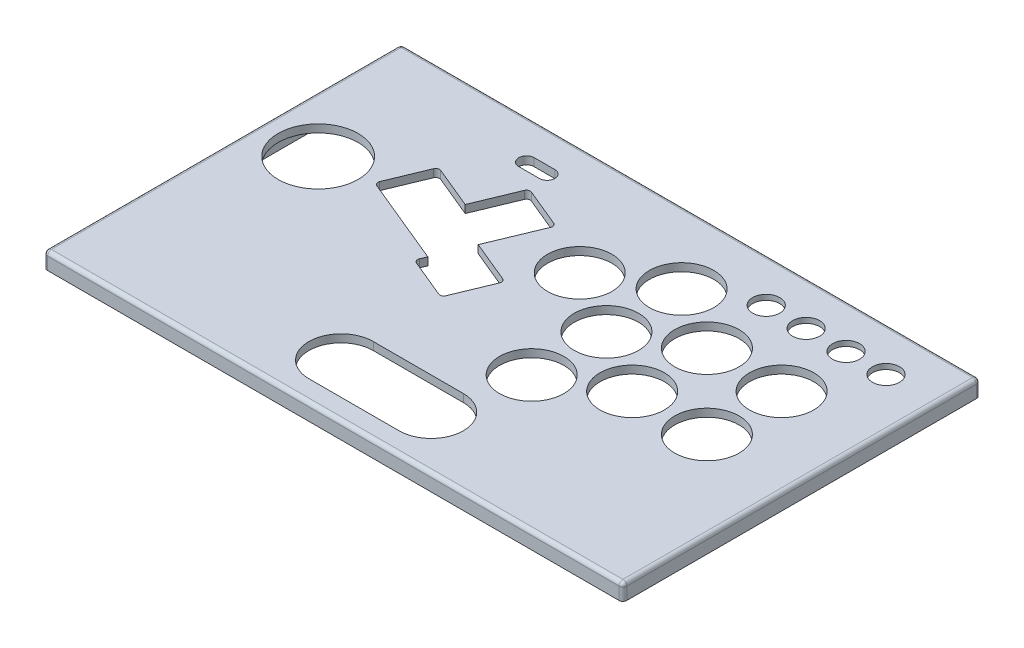
SolidWorks part; units mm, degrees
ref_plane "Front Plane" through (0, 0, 0) normal (0, 0, 1) x (1, 0, 0)
ref_plane "Top Plane" through (0, 0, 0) normal (0, 1, 0) x (1, 0, 0)
ref_plane "Right Plane" through (0, 0, 0) normal (1, 0, 0) x (0, 0, -1)
sketch "Button Cutouts" plane through (0, 0, 0) normal (0, 1, 0) x (1, 0, 0)
  line L0 (24.5, 61) -> (24.5, 32) construction
  line L1 (298.8548, 529.5585) -> (1494.2739, 529.5585) construction
  line L12 (-36.2591, 48.1292) -> (-29.3708, 64.7591) construction
  line L20 (49.5, 75) -> (49.5, 46) construction
  line L21 (78.5, 75) -> (78.5, 46) construction
  line L22 (17.5, 0) -> (-17.5, 0) construction
  line L28 (-36.2591, 48.1292) -> (-19.6292, 41.2409) construction
  line L29 (17.5, -12.5) -> (-17.5, -12.5)
  line L30 (17.5, 12.5) -> (-17.5, 12.5)
  line L31 (24.6803, 89.9994) -> (49.5, 75) construction
  line L32 (24.6803, 89.9994) -> (24.5, 61) construction
  line L33 (-0.5241, 75.6559) -> (24.6803, 89.9994) construction
  line L34 (-0.5241, 75.6559) -> (24.5, 61) construction
  line L48 (-29.3708, 64.7591) -> (-12.7409, 57.8708) construction
  line L49 (-19.6292, 41.2409) -> (-12.7409, 57.8708) construction
  line L50 (-36.2591, 48.1292) -> (-12.7409, 57.8708) construction
  line L51 (-29.3708, 64.7591) -> (-19.6292, 41.2409) construction
  line L52 (-35.6984, 52.2266) -> (-28.8101, 68.8564) construction
  line L53 (-35.6984, 52.2266) -> (-52.3282, 59.1149) construction
  line L54 (-28.8101, 68.8564) -> (-45.4399, 75.7447) construction
  line L55 (-52.3282, 59.1149) -> (-45.4399, 75.7447) construction
  line L56 (-35.6984, 52.2266) -> (-45.4399, 75.7447) construction
  line L57 (-28.8101, 68.8564) -> (-52.3282, 59.1149) construction
  line L58 (-69.9281, 66.405) -> (-63.0398, 83.0348) construction
  line L59 (-69.9281, 66.405) -> (-53.2983, 59.5167) construction
  line L60 (-63.0398, 83.0348) -> (-46.41, 76.1465) construction
  line L61 (-53.2983, 59.5167) -> (-46.41, 76.1465) construction
  line L62 (-69.9281, 66.405) -> (-46.41, 76.1465) construction
  line L63 (-63.0398, 83.0348) -> (-53.2983, 59.5167) construction
  line L64 (-40.5692, 63.9856) -> (-22.9693, 56.6955) construction
  line L65 (-40.5692, 63.9856) -> (-58.1691, 71.2758) construction
  line L66 (-45.0381, 76.7148) -> (-38.1498, 93.3446) construction
  line L67 (-45.0381, 76.7148) -> (-28.4083, 69.8265) construction
  line L68 (-38.1498, 93.3446) -> (-21.52, 86.4563) construction
  line L69 (-28.4083, 69.8265) -> (-21.52, 86.4563) construction
  line L70 (-45.0381, 76.7148) -> (-21.52, 86.4563) construction
  line L71 (-38.1498, 93.3446) -> (-28.4083, 69.8265) construction
  line L72 (-40.5692, 63.9856) -> (-33.2791, 81.5855) construction
  line L73 (-24.5, 53) -> (-22.9693, 56.6955) construction
  line L74 (-58.1691, 71.2758) -> (-65.4592, 53.6759) construction
  line L75 (-65.4592, 53.6759) -> (-90.4039, 64.0083) construction
  line L76 (-70.5814, 66.1344) -> (-63.3104, 83.6881)
  line L77 (-63.3104, 83.6881) -> (-45.7105, 76.398)
  line L78 (-45.7105, 76.398) -> (-38.4204, 93.9979)
  line L79 (-38.4204, 93.9979) -> (-20.8667, 86.7269)
  line L80 (-20.8667, 86.7269) -> (-29.6876, 65.4315)
  line L81 (-29.6876, 65.4315) -> (-12.0877, 58.1414)
  line L82 (-12.0877, 58.1414) -> (-19.3586, 40.5877)
  line L83 (-19.3586, 40.5877) -> (-36.9123, 47.8586)
  line L84 (-36.9123, 47.8586) -> (-35.3816, 51.5542)
  line L85 (-35.3816, 51.5542) -> (-70.5814, 66.1344)
  line L86 (-66.484, 74.7199) -> (-66.9459, 74.9112) construction
  line L87 (-29.6436, 90.3624) -> (-29.8349, 89.9005) construction
  line L88 (-16.1851, 49.5558) -> (-15.7231, 49.3645) construction
  line L89 (-33.2791, 140.3317) -> (-33.2791, 81.5855) construction
  circle A0 centre (24.5, 32) radius 12.5
  circle A1 centre (24.5, 61) radius 12.5
  circle A2 centre (49.5, 46) radius 12.5
  circle A3 centre (49.5, 75) radius 12.5
  circle A4 centre (78.5, 75) radius 12.5
  circle A5 centre (78.5, 46) radius 12.5
  arc A8 (17.5, -12.5) -> (17.5, 12.5) centre (17.5, 0) ccw
  arc A9 (-17.5, 12.5) -> (-17.5, -12.5) centre (-17.5, 0) ccw
  circle A10 centre (-90.4039, 64.0083) radius 15.5
  circle A11 centre (24.6803, 89.9994) radius 12.5
  circle A12 centre (-0.5241, 75.6559) radius 12.5
  point P1 (-24.5, 53)
  point P5 (-40.5692, 63.9856)
  point P6 (-58.1691, 71.2758)
  point P37 (0, 0)
  point P45 (-33.2791, 81.5855)
  point P54 (-30, 0)
  point P55 (30, 0)
  dimension "D2" = 25
  dimension "D12" = 12.5
  dimension "D18" = 31
  dimension "D25" = 22.5
  dimension "D1" = 29
  dimension "D3" = 25
  dimension "D4" = 29
  dimension "D5" = 14
  dimension "D6" = 18
  dimension "D7" = 19.05
  dimension "D8" = 53
  dimension "D9" = 7
  dimension "D10" = 4
  dimension "D11" = 27
  dimension "D13" = 32
  dimension "D14" = 7
  dimension "D15" = 19.05
  dimension "D16" = 0.5
  dimension "D17" = 60
  dimension "D19" = 0.5
  dimension "D20" = 0.5
  dimension "D21" = 29
  dimension "D22" = 29
  dimension "D23" = 0.5
  dimension "D24" = 0.5
sketch "Sketch2" plane through (0, 0, 0) normal (0, 1, 0) x (1, 0, 0)
  line L0 (-105.9039, 64.0083) -> (-112.4039, 64.0083) construction
  line L1 (-112.4039, 118.1994) -> (112.4039, 118.1994)
  line L2 (-112.4039, 118.1994) -> (-112.4039, -20.5)
  line L3 (-112.4039, -20.5) -> (112.4039, -20.5)
  line L4 (112.4039, 118.1994) -> (112.4039, -20.5)
  line L5 (24.6803, 102.4994) -> (24.6803, 118.1994) construction
  line L6 (0, -12.5) -> (0, -20.5) construction
  line L7 (17.5, -12.5) -> (-17.5, -12.5) construction
  circle A0 centre (-90.4039, 64.0083) radius 15.5 construction
  circle A2 centre (24.6803, 89.9994) radius 12.5 construction
  point P4 (0, -20.5)
  dimension "D2" = 6.5
  dimension "D1" = 8
  dimension "D3" = 15.7
  dimension "D4" = 224.8079
  dimension "D5" = 138.6994
extrude "top plate" add sketch "Sketch2" along normal blind 6.35
extrude "primary button cutouts" cut sketch "Button Cutouts" along normal up to next
fillet "Fillet1" radius 1.5 7 edges at (-20.8667, 3.175, -86.7269) (-12.0877, 3.175, -58.1414) (-19.3586, 3.175, -40.5877) (-36.9123, 3.175, -47.8586) (-70.5814, 3.175, -66.1344) (-63.3104, 3.175, -83.6881) (-38.4204, 3.175, -93.9979)
sketch "Sketch4" plane through (0, 0, 0) normal (0, -1, 0) x (1, 0, 0)
  line L0 (112.4039, 20.5) -> (112.4039, -118.1994) construction
  line L1 (-106.4039, 14.5) -> (106.4039, 14.5)
  line L2 (-106.4039, 14.5) -> (-106.4039, -112.1994)
  line L3 (-106.4039, -112.1994) -> (106.4039, -112.1994)
  line L4 (106.4039, 14.5) -> (106.4039, -112.1994)
  line L5 (-112.4039, 20.5) -> (112.4039, 20.5) construction
  line L6 (112.4039, -118.1994) -> (-112.4039, -118.1994) construction
  line L7 (-112.4039, -118.1994) -> (-112.4039, 20.5) construction
  dimension "D1" = 6
  dimension "D2" = 6
  dimension "D3" = 6
  dimension "D4" = 6
extrude "Cut-Extrude2" cut sketch "Sketch4" against normal blind 3.3
fillet "Fillet2" radius 1.5 8 edges at (112.4039, 3.175, -118.1994) (-112.4039, 3.175, -118.1994) (-112.4039, 3.175, 20.5) (112.4039, 3.175, 20.5) (112.4039, 6.35, -48.8497) (0, 6.35, -118.1994) (0, 6.35, 20.5) (-112.4039, 6.35, -48.8497)
hole_wizard "Tap Drill for M3x0.5 Tap1" positions "3DSketch1" profile "Sketch6" hole size "M3x0.5" standard "ANSI Metric"
sketch3d "3DSketch1"
  line L0 (-108.4039, 0, 16.5) -> (-108.4039, 0, 20.5) construction
  line L1 (-110.9039, 0, 20.5) -> (110.9039, 0, 20.5) construction
  line L3 (-108.4039, 0, 16.5) -> (-112.4039, 0, 16.5)
  line L4 (-112.4039, 0, -116.6994) -> (-112.4039, 0, 19) construction
  line L6 (108.4039, 0, -114.1994) -> (112.4039, 0, -114.1994)
  line L7 (112.4039, 0, 19) -> (112.4039, 0, -116.6994) construction
  line L9 (108.4039, 0, -114.1994) -> (108.4039, 0, -118.1994)
  line L10 (110.9039, 0, -118.1994) -> (-110.9039, 0, -118.1994) construction
  point P0 (-108.4039, 0, 16.5)
  point P2 (-108.4039, 0, -114.1994)
  point P4 (108.4039, 0, -114.1994)
  point P6 (108.4039, 0, 16.5)
  dimension "D1" = 4
sketch "Sketch6" plane through (-108.4039, 0, 16.5) normal (1, 0, 0) x (0, 0, -1)
  line L0 (0, 0) -> (0, 4.7511)
  line L1 (0, 4.7511) -> (1.25, 4)
  line L2 (1.25, 4) -> (1.25, 0)
  line L5 (1.25, 0) -> (0, 0)
  line L10 (0, 4.7511) -> (-1.25, 4) construction
  line L11 (0, -6.35) -> (0, 107.95) construction
  dimension "Hole Dia." = 2.5
  dimension "Hole Depth" = 4
  dimension "Drill Angle" = 118
sketch "Sketch7" plane through (0, 6.35, 0) normal (0, 1, 0) x (1, 0, 0)
  circle A0 centre (46.5961, 100.92) radius 5.25
  circle A1 centre (62.0961, 100.92) radius 5.25
  circle A2 centre (77.5961, 100.92) radius 5.25
  circle A3 centre (93.0961, 100.92) radius 5.25
  dimension "D1" = 10.5
extrude "extra_buttons" cut sketch "Sketch7" against normal up to next
sketch "Sketch8" plane through (0, 6.35, 0) normal (0, 1, 0) x (1, 0, 0)
  line L0 (-48.0625, 102.5336) -> (-40.0625, 102.5336) construction
  line L1 (-48.0625, 105.5336) -> (-40.0625, 105.5336)
  line L2 (-48.0625, 99.5336) -> (-40.0625, 99.5336)
  arc A0 (-48.0625, 105.5336) -> (-48.0625, 99.5336) centre (-48.0625, 102.5336) ccw
  arc A1 (-40.0625, 99.5336) -> (-40.0625, 105.5336) centre (-40.0625, 102.5336) ccw
  point P2 (-44.0625, 102.5336)
  dimension "D1" = 8
  dimension "D2" = 6
extrude "led_cutout" cut sketch "Sketch8" against normal up to next
sketch "Sketch9" plane through (0, 3.3, 0) normal (0, -1, 0) x (-1, 0, 0)
  line L0 (-93.0961, 100.92) -> (-46.5961, 100.92) construction
  line L1 (-93.0961, 110.92) -> (-46.5961, 110.92)
  line L2 (-93.0961, 90.92) -> (-46.5961, 90.92)
  arc A0 (-93.0961, 110.92) -> (-93.0961, 90.92) centre (-93.0961, 100.92) ccw
  arc A1 (-46.5961, 90.92) -> (-46.5961, 110.92) centre (-46.5961, 100.92) ccw
  circle A2 centre (-93.0961, 100.92) radius 5.25 construction
  circle A3 centre (-46.5961, 100.92) radius 5.25 construction
  point P2 (-69.8461, 100.92)
  point P7 (0, 0)
  point P10 (0, 0)
  dimension "D1" = 10
extrude "Cut-Extrude3" cut sketch "Sketch9" against normal blind 1
